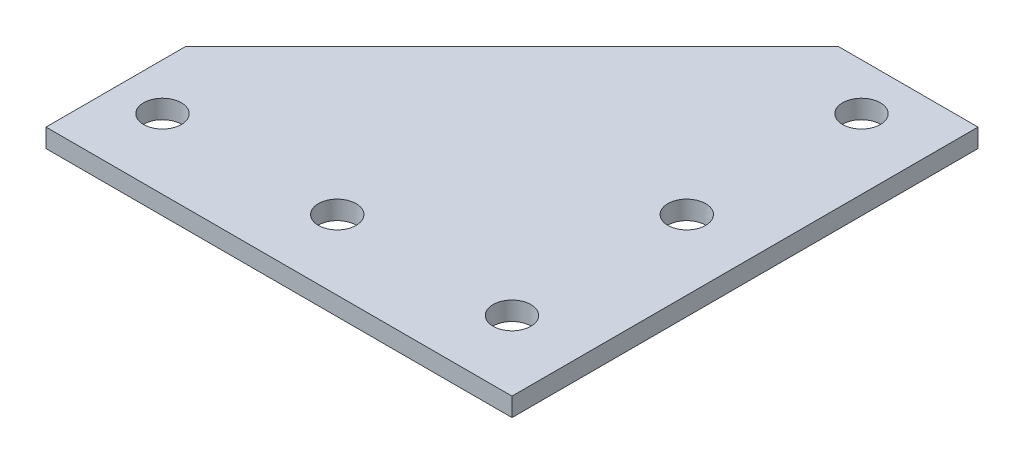
SolidWorks part; units mm, degrees
material "6061-T6 (SS)"
ref_plane "Front Plane" through (0, 0, 0) normal (0, 0, 1) x (1, 0, 0)
ref_plane "Top Plane" through (0, 0, 0) normal (0, 1, 0) x (1, 0, 0)
ref_plane "Right Plane" through (0, 0, 0) normal (1, 0, 0) x (0, 0, -1)
sketch "Sketch1" plane through (0, 0, 0) normal (0, 1, 0) x (1, 0, 0)
  line L0 (0, 0) -> (-75, 0) construction
  line L1 (0, 0) -> (0, 75) construction
  line L2 (15, -15) -> (-85, -15)
  line L3 (15, -15) -> (15, 85)
  line L4 (-85, -15) -> (-85, 15)
  line L5 (-85, 15) -> (-15, 85)
  line L6 (-15, 85) -> (15, 85)
  circle A0 centre (-75, 0) radius 4.05
  circle A1 centre (-37.5, 0) radius 4.05
  circle A2 centre (0, 0) radius 4.05
  circle A3 centre (0, 75) radius 4.05
  circle A4 centre (0, 37.5) radius 4.05
  dimension "D1" = 8.1
  dimension "D2" = 75
  dimension "D3" = 15
  dimension "D4" = 15
  dimension "D5" = 30
  dimension "D6" = 10
extrude "Boss-Extrude1" add sketch "Sketch1" along normal blind 4
